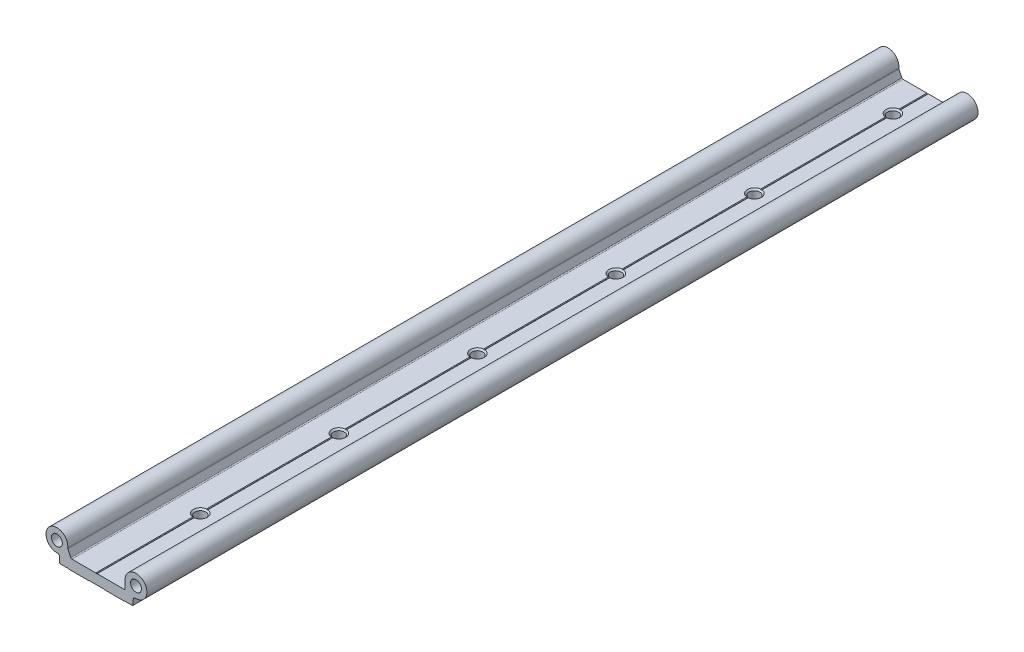
SolidWorks part; units mm, degrees
ref_plane "Front Plane" through (0, 0, 0) normal (0, 0, 1) x (1, 0, 0)
ref_plane "Top Plane" through (0, 0, 0) normal (0, 1, 0) x (1, 0, 0)
ref_plane "Right Plane" through (0, 0, 0) normal (1, 0, 0) x (0, 0, -1)
sketch "Model" plane through (0, 0, 0) normal (0, 0, 1) x (1, 0, 0)
  line L0 (0, 0.2) -> (0, 7.5) construction
  line L1 (0, 0.2) -> (0, 7.5) construction
  line L2 (0, 0.2) -> (0, 7.5) construction
  line L3 (0, 0.2) -> (0, 7.5) construction
  line L4 (-33, 14) -> (-25, 14) construction
  line L5 (25, 14) -> (33, 14) construction
  line L6 (-29, 22) -> (-29, 6) construction
  line L7 (-37, 14) -> (-21, 14) construction
  line L8 (29, 22) -> (29, 6) construction
  line L9 (21, 14) -> (37, 14) construction
  line L10 (-18.8438, 7.9819) -> (-20.9669, 12.5349)
  line L11 (6, 0) -> (5.8, 0.2)
  line L12 (-26.5, 0.2) -> (-27, 0.7)
  line L13 (-20, 0) -> (-20.2, 0.2)
  line L14 (0, 7.2113) -> (-0.5, 7.5)
  line L15 (6, 0) -> (20, 0)
  line L16 (-20, 0) -> (-6, 0)
  line L17 (-5.8, 0.2) -> (5.8, 0.2)
  line L18 (20.2, 0.2) -> (26.5, 0.2)
  line L19 (-26.5, 0.2) -> (-20.2, 0.2)
  line L20 (0.5, 7.5) -> (17.9885, 7.5)
  line L21 (-17.9885, 7.5) -> (-0.5, 7.5)
  line L22 (0, 7.2113) -> (0.5, 7.5)
  line L23 (20, 0) -> (20.2, 0.2)
  line L24 (-6, 0) -> (-5.8, 0.2)
  line L25 (26.5, 0.2) -> (27, 0.7)
  line L26 (18.8438, 7.9819) -> (20.9669, 12.5349)
  line L27 (-27, 0.7) -> (-27, 4.5132)
  line L28 (27, 0.7) -> (27, 4.5132)
  circle A0 centre (-29, 14) radius 4
  arc A1 (-21.0538, 13.0733) -> (-28.5789, 6.0111) centre (-29, 14) ccw
  arc A2 (-27, 4.5132) -> (-28.5789, 6.0111) centre (-28.5, 4.5132) ccw
  arc A3 (-21.0538, 13.0733) -> (-20.9669, 12.5349) centre (-20.0606, 12.9575) ccw
  arc A4 (-18.8438, 7.9819) -> (-17.9885, 7.5) centre (-17.9885, 8.5) ccw
  arc A5 (17.9885, 7.5) -> (18.8438, 7.9819) centre (17.9885, 8.5) ccw
  arc A6 (20.9669, 12.5349) -> (21.0538, 13.0733) centre (20.0606, 12.9575) ccw
  arc A7 (28.5789, 6.0111) -> (27, 4.5132) centre (28.5, 4.5132) ccw
  circle A8 centre (29, 14) radius 4
  arc A9 (28.5789, 6.0111) -> (21.0538, 13.0733) centre (29, 14) ccw
  dimension "D1" = 8
  dimension "D2" = 8
  dimension "D3" = 1.5
  dimension "D4" = 1
  dimension "D5" = 0.5
  dimension "D6" = 5.8
  dimension "D7" = 6
  dimension "D8" = 17.9885
  dimension "D9" = 18.8438
  dimension "D10" = 20
  dimension "D11" = 20.0606
  dimension "D12" = 20.9669
  dimension "D13" = 21.0538
  dimension "D14" = 26.5
  dimension "D15" = 27
  dimension "D16" = 4.5132
  dimension "D17" = 7.2113
extrude "Boss-Extrude1" add sketch "Model" along normal blind 609.6
hole_wizard "3/8-16 Tapped Hole1" positions "Sketch1" profile "Sketch2" tap size "3/8-16" standard "ANSI Inch" end condition through all
sketch "Sketch1" plane through (0, 7.5, 0) normal (0, 1, 0) x (1, 0, 0)
  line L0 (0, -609.6) -> (0, 0) construction
  line L1 (-0.5, 0) -> (-17.9885, 0) construction
  point P0 (0, -25.4)
  point P21 (0, -127)
  point P22 (0, -228.6)
  point P23 (0, -330.2)
  point P24 (0, -431.8)
  point P25 (0, -533.4)
  point P26 (0, -635)
  point P27 (0, -736.6)
  point P28 (0, -838.2)
  point P29 (0, -939.8)
  point P30 (0, -1041.4)
  point P31 (0, -1143)
  point P32 (0, -1244.6)
  point P33 (0, -1346.2)
  point P34 (0, -1447.8)
  point P35 (0, -1549.4)
  point P36 (0, -1651)
  point P37 (0, -1752.6)
  point P38 (0, -1854.2)
  point P39 (0, -1955.8)
  dimension "D1" = 25.4
  dimension "D2" = 20
sketch "Sketch2" plane through (0, 7.5, 25.4) normal (1, 0, 0) x (0, 0, 1)
  line L0 (0, 0) -> (0, 7.5)
  line L1 (0, 7.5) -> (3.9687, 7.5)
  line L2 (3.9687, 7.5) -> (3.9687, 1.1113)
  line L3 (3.9687, 1.1113) -> (5.08, 0)
  line L5 (5.08, 0) -> (0, 0)
  line L6 (-3.9687, 1.1112) -> (-5.08, 0) construction
  line L11 (0, -6.35) -> (0, 107.95) construction
  dimension "Thread Major Dia." = 7.9375
  dimension "Thru Tap Drill Depth" = 7.5
  dimension "Near C'Sink Dia." = 10.16
  dimension "Near C'Sink Angle" = 90
sketch "Sketch3" plane through (0, 0, 0) normal (0, 0, -1) x (-1, 0, 0)
  line L0 (-17.9885, 7.5) -> (-21.0538, 7.5)
  line L2 (-21.0538, 13.0733) -> (-21.0538, 7.5)
  line L3 (-21.0538, 13.0733) -> (-17.9885, 7.5)
extrude "Cut-Extrude1" cut sketch "Sketch3" against normal through all
hole_wizard "Tap Drill for #0-80 Tap1" positions "Sketch4" profile "Sketch6" hole size "#0-80" standard "ANSI Inch" end condition through all
sketch "Sketch4" plane through (0, 7.5, 0) normal (0, 1, 0) x (1, 0, 0)
  point P0 (19.4028, -3.3098)
  point P12 (19.4028, -103.0556)
  point P13 (19.4028, -202.8014)
  point P14 (19.4028, -302.5472)
  point P15 (19.4028, -402.293)
  point P16 (19.4028, -502.0388)
  point P17 (19.4028, -601.7846)
  point P18 (19.4028, -701.5304)
  point P19 (19.4028, -801.2762)
  point P20 (19.4028, -901.022)
  dimension "D1" = 10
  dimension "D2" = 103.0556
sketch "Sketch6" plane through (19.4028, 7.5, 3.3098) normal (1, 0, 0) x (0, 0, 1)
  line L0 (0, 0) -> (0, 7.5)
  line L1 (0, 7.5) -> (0.5956, 7.5)
  line L2 (0.5956, 7.5) -> (0.5956, 0)
  line L5 (0.5956, 0) -> (0, 0)
  line L11 (0, -6.35) -> (0, 107.95) construction
  dimension "Thru Hole Dia." = 1.1913
  dimension "Thru Hole Depth" = 7.5
